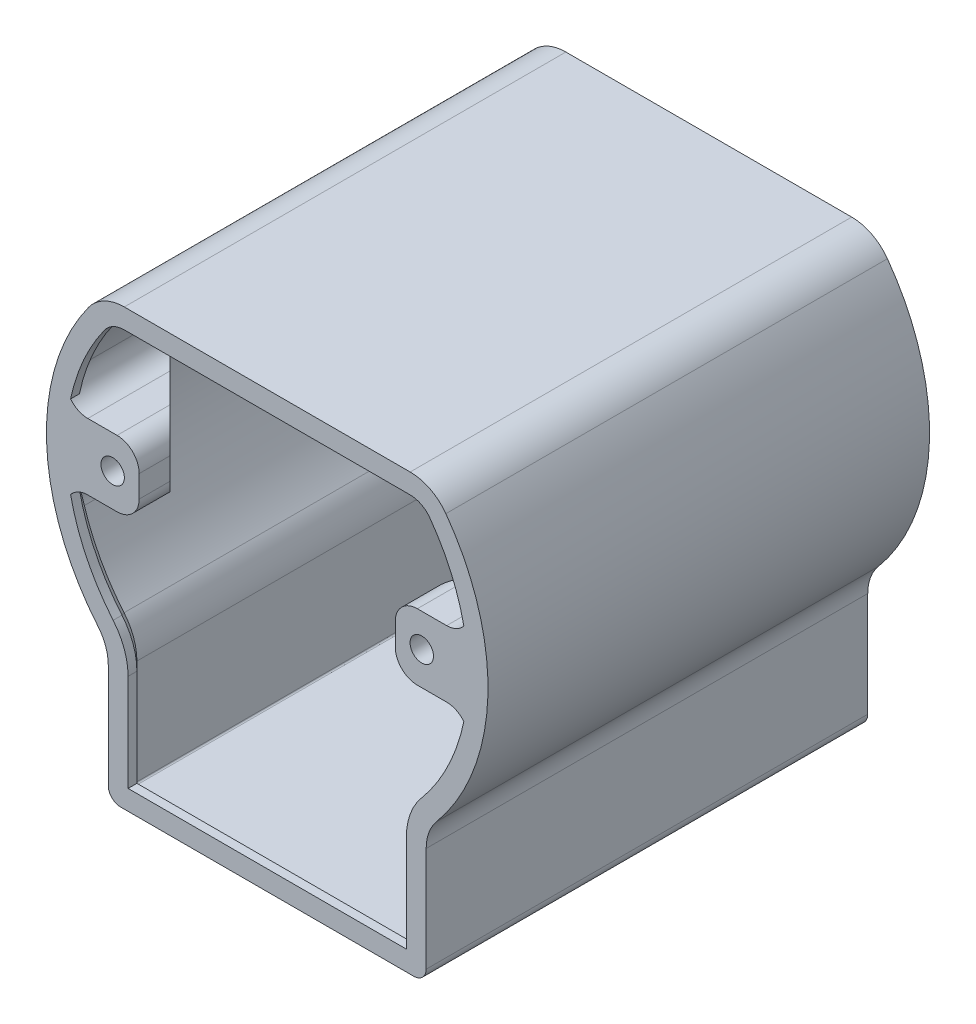
SolidWorks part; units mm, degrees
ref_plane "Ebene vorne" through (0, 0, 0) normal (0, 0, 1) x (1, 0, 0)
ref_plane "Ebene oben" through (0, 0, 0) normal (0, 1, 0) x (1, 0, 0)
ref_plane "Ebene rechts" through (0, 0, 0) normal (1, 0, 0) x (0, 0, -1)
sketch "Skizze1" plane through (0, 0, 0) normal (0, 0, 1) x (1, 0, 0)
  line L0 (0, 15.499) -> (0, -28.3741) construction
  line L1 (0, 33.5) -> (-32.369, 33.5)
  line L2 (0, 33.5) -> (32.369, 33.5)
  line L3 (-36, -38.5227) -> (-36, -62.2)
  line L4 (-33.2, -65) -> (0, -65)
  line L5 (-50, 78.1636) -> (-50, -33.9451) construction
  line L6 (50, 78.1636) -> (50, -33.9451) construction
  line L7 (-50, 0) -> (50, 0) construction
  line L8 (36, -38.5227) -> (36, -62.2)
  line L10 (0, -65) -> (33.2, -65)
  arc A0 (-40.4612, 29.375) -> (-38.3333, -32.1023) centre (0, 0) ccw
  arc A3 (40.4612, 29.375) -> (38.3333, -32.1023) centre (0, 0) cw
  arc A8 (32.369, 33.5) -> (40.4612, 29.375) centre (32.369, 23.5) cw
  arc A9 (-32.369, 33.5) -> (-40.4612, 29.375) centre (-32.369, 23.5) ccw
  arc A10 (38.3333, -32.1023) -> (36, -38.5227) centre (46, -38.5227) ccw
  arc A11 (-38.3333, -32.1023) -> (-36, -38.5227) centre (-46, -38.5227) cw
  arc A12 (36, -62.2) -> (33.2, -65) centre (33.2, -62.2) cw
  arc A13 (-36, -62.2) -> (-33.2, -65) centre (-33.2, -62.2) ccw
  point P18 (0, 0)
  point P34 (36, -65)
  point P37 (-36, -65)
  dimension "D1" = 72
  dimension "D4" = 10
  dimension "D2" = 10
  dimension "D7" = 2.8
  dimension "D3" = 65
  dimension "D5" = 33.5
  dimension "D6" = 100
extrude "Linear-Austragen-Dünn1" add sketch "Skizze1" along normal blind 100 thin thin type one direction reverse wall 2.49
sketch "Skizze16" plane through (0, 0, 100) normal (0, 0, 1) x (1, 0, 0)
  line L0 (33.51, -62.2) -> (33.51, -38.5227) construction
  line L1 (32.369, 31.01) -> (-32.369, 31.01) construction
  line L2 (-33.51, -38.5227) -> (-33.51, -62.2) construction
  line L3 (-33.2, -62.51) -> (33.2, -62.51) construction
  line L4 (33.51, -62.2) -> (33.51, -38.5227)
  line L5 (32.369, 31.01) -> (-32.369, 31.01)
  line L6 (-33.51, -38.5227) -> (-33.51, -62.2)
  line L7 (-33.2, -62.51) -> (33.2, -62.51)
  arc A0 (33.2, -62.51) -> (33.51, -62.2) centre (33.2, -62.2) ccw construction
  arc A1 (36.4243, -30.5036) -> (33.51, -38.5227) centre (46, -38.5227) ccw construction
  arc A2 (36.4243, -30.5036) -> (38.4462, 27.9121) centre (0, 0) ccw construction
  arc A3 (38.4462, 27.9121) -> (32.369, 31.01) centre (32.369, 23.5) ccw construction
  arc A4 (-32.369, 31.01) -> (-38.4462, 27.9121) centre (-32.369, 23.5) ccw construction
  arc A5 (-38.4462, 27.9121) -> (-36.4243, -30.5036) centre (0, 0) ccw construction
  arc A6 (-33.51, -38.5227) -> (-36.4243, -30.5036) centre (-46, -38.5227) ccw construction
  arc A7 (-33.51, -62.2) -> (-33.2, -62.51) centre (-33.2, -62.2) ccw construction
  arc A8 (33.2, -62.51) -> (33.51, -62.2) centre (33.2, -62.2) ccw
  arc A9 (36.4243, -30.5036) -> (33.51, -38.5227) centre (46, -38.5227) ccw
  arc A10 (36.4243, -30.5036) -> (38.4462, 27.9121) centre (0, 0) ccw
  arc A11 (38.4462, 27.9121) -> (32.369, 31.01) centre (32.369, 23.5) ccw
  arc A12 (-32.369, 31.01) -> (-38.4462, 27.9121) centre (-32.369, 23.5) ccw
  arc A13 (-38.4462, 27.9121) -> (-36.4243, -30.5036) centre (0, 0) ccw
  arc A14 (-33.51, -38.5227) -> (-36.4243, -30.5036) centre (-46, -38.5227) ccw
  arc A15 (-33.51, -62.2) -> (-33.2, -62.51) centre (-33.2, -62.2) ccw
sketch "Skizze17" plane through (0, 0, 0) normal (1, 0, 0) x (0, 0, -1)
  line L0 (-100, 31.01) -> (-100, 29.01)
  line L1 (-100, 27.9121) -> (-100, -30.5036) construction
  line L3 (-100, 31.01) -> (0, 31.01) construction
  line L4 (-96, 31.01) -> (-100, 31.01)
  line L5 (-100, 29.01) -> (-98, 29.01)
  line L6 (-98, 29.01) -> (-96, 31.01)
  line L7 (-100, 27.9121) -> (-100, -30.5036) construction
  line L8 (-100, 31.01) -> (-100, -62.51) construction
  line L9 (-100, -62.2) -> (-100, -62.51) construction
  line L10 (-100, -62.2) -> (-100, -65) construction
  line L11 (-100, -15.75) -> (0, -15.75) construction
  line L12 (0, -30.5036) -> (0, 27.9121) construction
  line L13 (-98, -60.51) -> (-96, -62.51)
  line L14 (-100, -60.51) -> (-98, -60.51)
  line L15 (-96, -62.51) -> (-100, -62.51)
  line L16 (-100, -62.51) -> (-100, -60.51)
  dimension "D1" = 45
  dimension "D2" = 2
  dimension "D3" = 2
sweep "Austragung2" add profiles "Skizze17" path "Skizze16"
sketch "Skizze6" plane through (0, 0, 0) normal (1, 0, 0) x (0, 0, -1)
  line L0 (-100, 29.375) -> (-100, -32.1023) construction
  line L1 (-100, 7.5) -> (-75, 7.5)
  line L2 (-100, 7.5) -> (-100, -7.5)
  line L3 (-100, -7.5) -> (-75, -7.5)
  line L4 (-75, 7.5) -> (-75, -7.5)
  line L5 (55, 0) -> (-55, 0) construction
  line L6 (0, -32.1023) -> (0, 29.375) construction
  line L7 (0, 7.5) -> (-25, 7.5)
  line L8 (0, 7.5) -> (0, -7.5)
  line L9 (0, -7.5) -> (-25, -7.5)
  line L10 (-25, 7.5) -> (-25, -7.5)
  point P6 (-100, 0)
  dimension "D1" = 15
  dimension "D2" = 25
  dimension "D3" = 25
extrude "Aufsatz-Linear austragen3" add sketch "Skizze6" along normal up to next from offset 29
mirror "Spiegeln1" about plane through (0, 0, 0) normal (1, 0, 0) of "Aufsatz-Linear austragen3"
chamfer "Fase1" distance 18 angle 45 4 edges at (29, 0, 75) (-29, 0, 75) (29, 0, 25) (-29, 0, 25)
sketch "Skizze2" plane through (0, 0, 100) normal (0, 0, -1) x (-1, 0, 0)
  line L0 (-32.369, 33.5) -> (32.369, 33.5) construction
  line L1 (36, -38.5227) -> (36, -62.2) construction
  line L2 (33.2, -65) -> (-33.2, -65) construction
  line L3 (-36, -62.2) -> (-36, -38.5227) construction
  line L4 (-32.369, 33.5) -> (32.369, 33.5)
  line L5 (36, -38.5227) -> (36, -62.2)
  line L6 (33.2, -65) -> (-33.2, -65)
  line L7 (-36, -62.2) -> (-36, -38.5227)
  line L8 (0, 31.01) -> (0, -62.51) construction
  line L9 (-28.75, 28.75) -> (28.75, 28.75)
  line L10 (-28.75, 28.75) -> (-28.75, -28.75)
  line L11 (-28.75, -28.75) -> (28.75, -28.75)
  line L12 (28.75, 28.75) -> (28.75, -28.75)
  line L13 (-28.75, 28.75) -> (28.75, -28.75) construction
  line L14 (-28.75, -28.75) -> (28.75, 28.75) construction
  line L15 (-28.75, -28.75) -> (28.75, -28.75)
  line L16 (-28.75, -28.75) -> (-28.75, -58.75)
  line L17 (-28.75, -58.75) -> (28.75, -58.75)
  line L18 (28.75, -28.75) -> (28.75, -58.75)
  line L19 (-32.369, 31.01) -> (32.369, 31.01) construction
  line L20 (33.2, -62.51) -> (-33.2, -62.51) construction
  arc A0 (-32.369, 33.5) -> (-40.4612, 29.375) centre (-32.369, 23.5) ccw construction
  arc A1 (40.4612, 29.375) -> (32.369, 33.5) centre (32.369, 23.5) ccw construction
  arc A2 (38.3333, -32.1023) -> (40.4612, 29.375) centre (0, 0) ccw construction
  arc A3 (38.3333, -32.1023) -> (36, -38.5227) centre (46, -38.5227) ccw construction
  arc A4 (33.2, -65) -> (36, -62.2) centre (33.2, -62.2) ccw construction
  arc A5 (-36, -62.2) -> (-33.2, -65) centre (-33.2, -62.2) ccw construction
  arc A6 (-36, -38.5227) -> (-38.3333, -32.1023) centre (-46, -38.5227) ccw construction
  arc A7 (-40.4612, 29.375) -> (-38.3333, -32.1023) centre (0, 0) ccw construction
  arc A8 (-32.369, 33.5) -> (-40.4612, 29.375) centre (-32.369, 23.5) ccw
  arc A9 (40.4612, 29.375) -> (32.369, 33.5) centre (32.369, 23.5) ccw
  arc A10 (38.3333, -32.1023) -> (40.4612, 29.375) centre (0, 0) ccw
  arc A11 (38.3333, -32.1023) -> (36, -38.5227) centre (46, -38.5227) ccw
  arc A12 (33.2, -65) -> (36, -62.2) centre (33.2, -62.2) ccw
  arc A13 (-36, -62.2) -> (-33.2, -65) centre (-33.2, -62.2) ccw
  arc A14 (-36, -38.5227) -> (-38.3333, -32.1023) centre (-46, -38.5227) ccw
  arc A15 (-40.4612, 29.375) -> (-38.3333, -32.1023) centre (0, 0) ccw
  circle A16 centre (-35, 0) radius 2.65
  circle A17 centre (35, 0) radius 2.65
  dimension "D3" = 70
  dimension "D4" = 5.3
  dimension "D1" = 57.5
  dimension "D2" = 30
sketch "Skizze7" plane through (0, 0, 100) normal (0, 0, 1) x (1, 0, 0)
  line L0 (0, 0) -> (0, 33.5) construction
  line L1 (32.369, 33.5) -> (-32.369, 33.5) construction
  circle A0 centre (-35, 0) radius 2.65
  circle A1 centre (35, 0) radius 2.65
  dimension "D1" = 5.3
  dimension "D2" = 70
extrude "Schnitt-Linear austragen3" cut sketch "Skizze7" against normal through all
sketch "Skizze9" plane through (0, 0, 100) normal (0, 0, 1) x (1, 0, 0)
  line L1 (-39.6188, 0) -> (-37.3094, -4)
  line L2 (-37.3094, -4) -> (-32.6906, -4)
  line L3 (-32.6906, -4) -> (-30.3812, 0)
  line L4 (-30.3812, 0) -> (-32.6906, 4)
  line L5 (-32.6906, 4) -> (-37.3094, 4)
  line L6 (-37.3094, 4) -> (-39.6188, 0)
  line L7 (30.3812, 0) -> (32.6906, -4)
  line L8 (32.6906, -4) -> (37.3094, -4)
  line L9 (37.3094, -4) -> (39.6188, 0)
  line L10 (39.6188, 0) -> (37.3094, 4)
  line L11 (37.3094, 4) -> (32.6906, 4)
  line L12 (32.6906, 4) -> (30.3812, 0)
  circle A2 centre (-35, 0) radius 4 construction
  circle A3 centre (35, 0) radius 4 construction
  dimension "D1" = 8
extrude "Schnitt-Linear austragen5" cut sketch "Skizze9" against normal blind 90 from offset 5 offset against normal yes
fillet "Verrundung1" radius 5 16 edges at (-46.9143, 7.5, 85.5429) (-29, 7.5, 96.5) (-29, -7.5, 96.5) (-46.9143, -7.5, 85.5429) (46.9143, -7.5, 85.5429) (29, -7.5, 96.5) (29, 7.5, 96.5) (46.9143, 7.5, 85.5429) (-46.9143, -7.5, 12.4571) (-29, -7.5, 3.5) (-29, 7.5, 3.5) (-46.9143, 7.5, 12.4571) (46.9143, -7.5, 12.4571) (29, -7.5, 3.5) (29, 7.5, 3.5) (46.9143, 7.5, 12.4571)
extrude "Aufsatz-Linear austragen5" add sketch "Skizze17<3>" against normal up to next and the other way up to next contours L13 L15 L16 L14
sketch "Skizze17<3>" plane through (0, 0, 0) normal (1, 0, 0) x (0, 0, -1) same geometry as "Skizze17"
